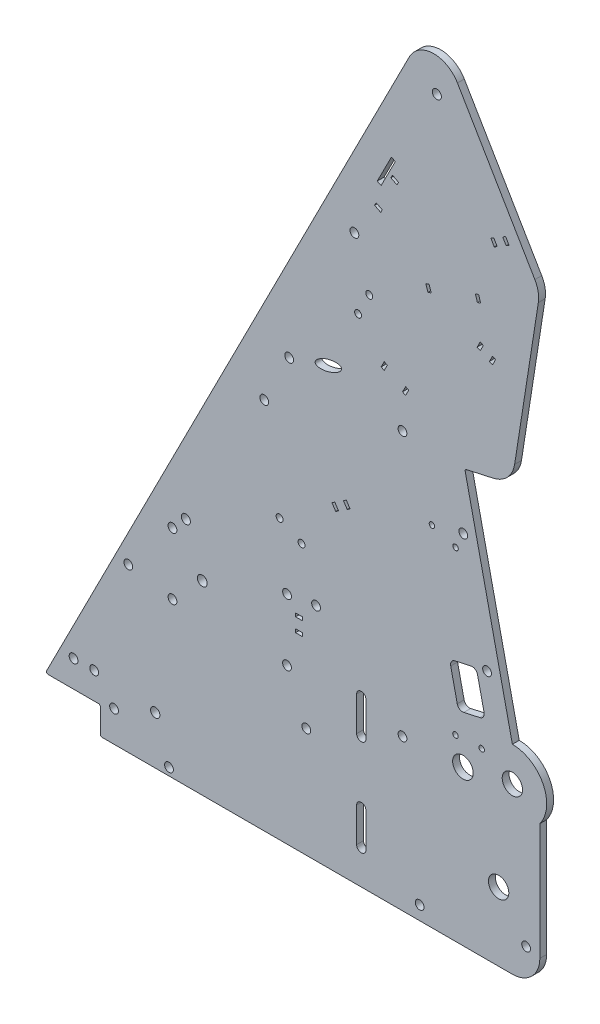
SolidWorks part; units mm, degrees
other "Markup1"
sketch "Sketch5"
ref_plane "Front Plane" through (0, 0, 0) normal (0, 0, 1) x (1, 0, 0)
ref_plane "Top Plane" through (0, 0, 0) normal (0, 1, 0) x (1, 0, 0)
ref_plane "Right Plane" through (0, 0, 0) normal (1, 0, 0) x (0, 0, -1)
sketch "Sketch1" plane through (0, 0, 0) normal (0, 0, 1) x (1, 0, 0)
  line L1 (228.6, -12.7) -> (228.6, 53.975)
  line L2 (178.7547, 351.4131) -> (0, 0)
  line L3 (228.6, 266.7) -> (178.7547, 351.4131)
  line L5 (0, 0) -> (25.4, 0)
  line L6 (25.4, 0) -> (25.4, -12.7)
  line L7 (25.4, -12.7) -> (228.6, -12.7)
  line L9 (215.9, 79.375) -> (193.9097, 178.5667)
  line L10 (193.9097, 178.5667) -> (215.6079, 183.377)
  line L11 (215.6079, 183.377) -> (228.6, 266.7)
  arc A0 (228.6, 53.975) -> (215.9, 79.375) centre (215.9, 63.5) ccw
  dimension "D7" = 12.7
  dimension "D8" = 76.2
  dimension "D10" = 31.75
  dimension "D2" = 279.4
  dimension "D3" = 25.4
  dimension "D4" = 215.9
  dimension "D5" = 394.2644
  dimension "D6" = 203.2
  dimension "D9" = 63.039
  dimension "D11" = 101.6
  dimension "D12" = 12.5
  dimension "D13" = 22.225
extrude "Boss-Extrude1" add sketch "Sketch1" along normal blind 3.175
sketch "Sketch2" plane through (0, 0, 3.175) normal (0, 0, 1) x (1, 0, 0)
  line L0 (178.7547, 351.4131) -> (0, 0) construction
  line L1 (25.4, -12.7) -> (228.6, -12.7) construction
  line L2 (215.9, 79.375) -> (193.9097, 178.5667) construction
  line L3 (193.9097, 178.5667) -> (215.6079, 183.377) construction
  line L4 (215.9, 79.375) -> (193.9097, 178.5667) construction
  line L5 (64.9432, 94.0578) -> (72.5445, 73.1732) construction
  line L6 (64.9432, 94.0578) -> (103.3734, 94.0578) construction
  line L10 (228.6, -12.7) -> (228.6, 53.975) construction
  circle A0 centre (64.9432, 94.0578) radius 2.0955
  circle A1 centre (180.975, 322.1643) radius 2.0955
  circle A2 centre (72.5445, 73.1732) radius 2.286
  circle A3 centre (193.2078, 152.3944) radius 2.032
  circle A4 centre (215.9, 63.5) radius 4.699
  circle A7 centre (173.0375, -6.35) radius 2.032
  circle A8 centre (204.203, 102.7985) radius 2.032
  circle A26 centre (209.55, 19.05) radius 4.699
  arc A30 (228.6, 53.975) -> (215.9, 79.375) centre (215.9, 63.5) ccw construction
  circle A31 centre (165.1, 179.3875) radius 2.032
  circle A35 centre (111.724, 87.4607) radius 2.032
  circle A36 centre (111.724, 58.8857) radius 2.032
  circle A37 centre (58.765, 58.8857) radius 2.032
  circle A38 centre (58.765, 87.4607) radius 2.032
  circle A39 centre (111.724, 58.8857) radius 1.905 construction
  circle A42 centre (111.724, 87.4607) radius 1.905 construction
  circle A43 centre (58.765, 58.8857) radius 1.905 construction
  circle A44 centre (58.765, 87.4607) radius 1.905 construction
  dimension "D3" = 4.191
  dimension "D5" = 4.191
  dimension "D9" = 4.572
  dimension "D20" = 9.398
  dimension "D23" = 9.398
  dimension "D18" = 4.064
  dimension "D26" = 4.064
  dimension "D14" = 4.064
  dimension "D10" = 4.064
  dimension "D2" = 15.24
  dimension "D6" = 15.24
  dimension "D7" = 22.225
  dimension "D21" = 44.45
  dimension "D22" = 6.35
  dimension "D19" = 160.3375
  dimension "D24" = 44.45
  dimension "D25" = 6.35
  dimension "D27" = 25.4
  dimension "D28" = 50.8
  dimension "D29" = 6.35
  dimension "D17" = 6.35
  dimension "D33" = 55.5625
  dimension "D15" = 114.3
  dimension "D4" = 180.975
  dimension "D8" = 70
extrude "Cut-Extrude1" cut sketch "Sketch2" against normal through all
sketch "Sketch7" plane through (0, 0, 3.175) normal (0, 0, 1) x (1, 0, 0)
  line L0 (146.05, 3.175) -> (146.05, 19.05) construction
  line L1 (143.891, 3.175) -> (143.891, 19.05)
  line L2 (148.209, 3.175) -> (148.209, 19.05)
  line L3 (146.05, 47.625) -> (146.05, 63.5) construction
  line L4 (143.891, 47.625) -> (143.891, 63.5)
  line L5 (148.209, 47.625) -> (148.209, 63.5)
  line L6 (25.4, -12.7) -> (228.6, -12.7) construction
  line L12 (228.6, -12.7) -> (228.6, 53.975) construction
  line L13 (25.4, -12.7) -> (228.6, -12.7) construction
  arc A0 (143.891, 3.175) -> (148.209, 3.175) centre (146.05, 3.175) ccw
  arc A1 (148.209, 19.05) -> (143.891, 19.05) centre (146.05, 19.05) ccw
  arc A2 (143.891, 47.625) -> (148.209, 47.625) centre (146.05, 47.625) ccw
  arc A3 (148.209, 63.5) -> (143.891, 63.5) centre (146.05, 63.5) ccw
  circle A8 centre (50.8, 9.525) radius 2.159
  point P2 (146.05, 11.1125)
  point P9 (146.05, 55.5625)
  dimension "D1" = 4.318
  dimension "D5" = 4.318
  dimension "D2" = 15.875
  dimension "D3" = 15.875
  dimension "D4" = 44.45
  dimension "D6" = 95.25
  dimension "D7" = 82.55
  dimension "D8" = 15.875
  dimension "D9" = 22.225
extrude "Cut-Extrude2" cut sketch "Sketch7" against normal through all
sketch "Sketch10" plane through (0, 0, 3.175) normal (0, 0, 1) x (1, 0, 0)
  circle A0 centre (120.65, 38.1) radius 2.032
  circle A1 centre (165.1, 57.15) radius 2.032
  circle A2 centre (13.0465, 12.3347) radius 2.032
  circle A3 centre (22.5715, 12.3347) radius 2.032
  circle A4 centre (38.3604, 62.564) radius 2.032
  circle A5 centre (13.0465, 12.3347) radius 2.032 construction
  circle A6 centre (22.5715, 12.3347) radius 2.032 construction
  dimension "D1" = 4.064
  dimension "D3" = 38.1
  dimension "D2" = 120.65
  dimension "D4" = 63.5
  dimension "D5" = 69.85
extrude "Cut-Extrude3" cut sketch "Sketch10" against normal up to next
fillet "Fillet1" radius 12.7 4 edges at (228.6, -12.7, 1.5875) (178.7547, 351.4131, 1.5875) (215.6079, 183.377, 1.5875) (228.6, 266.7, 1.5875)
fillet "Fillet2" radius 0.7937 4 edges at (25.4, -12.7, 1.5875) (25.4, 0, 1.5875) (193.9097, 178.5667, 1.5875) (0, 0, 1.5875)
sketch "Sketch12" plane through (0, 0, 3.175) normal (0, 0, 1) x (1, 0, 0)
  circle A0 centre (31.75, 1.5875) radius 2.032
  circle A1 centre (173.0375, -6.35) radius 2.032
  circle A2 centre (222.25, 1.5875) radius 2.032
  circle A3 centre (57.15, -9.2075) radius 2.032
  circle A4 centre (57.15, -9.2075) radius 2.286 construction
  dimension "D1" = 4.064
  dimension "D2" = 4.064
extrude "Cut-Extrude5" cut sketch "Sketch12" against normal through all
sketch "Sketch13" plane through (0, 0, 3.175) normal (0, 0, 1) x (1, 0, 0)
  line L1 (228.6, 0) -> (228.6, 53.975) construction
  line L3 (26.1937, -12.7) -> (215.9, -12.7) construction
  line L8 (177.4093, 244.3006) -> (175.8978, 243.8153)
  line L9 (178.3799, 241.2777) -> (177.4093, 244.3006)
  line L10 (176.8684, 240.7923) -> (178.3799, 241.2777)
  line L11 (175.8978, 243.8153) -> (176.8684, 240.7923)
  line L12 (177.4093, 244.3006) -> (175.8978, 243.8153)
  line L13 (178.3799, 241.2777) -> (177.4093, 244.3006)
  line L14 (176.8684, 240.7923) -> (178.3799, 241.2777)
  line L15 (175.8978, 243.8153) -> (176.8684, 240.7923)
  line L16 (159.9872, 286.5068) -> (153.4231, 273.6024)
  line L17 (199.7492, 248.1392) -> (201.2607, 248.6245)
  line L18 (198.7785, 251.1622) -> (199.7492, 248.1392)
  line L19 (200.29, 251.6475) -> (198.7785, 251.1622)
  line L20 (201.2607, 248.6245) -> (200.29, 251.6475)
  line L21 (199.7492, 248.1392) -> (201.2607, 248.6245)
  line L22 (198.7785, 251.1622) -> (199.7492, 248.1392)
  line L23 (200.29, 251.6475) -> (198.7785, 251.1622)
  line L24 (201.2607, 248.6245) -> (200.29, 251.6475)
  line L25 (159.9872, 286.5068) -> (161.7699, 285.6001)
  line L26 (159.73, 278.0885) -> (162.5599, 276.649)
  line L27 (160.4498, 279.5035) -> (159.73, 278.0885)
  line L28 (163.2797, 278.0639) -> (160.4498, 279.5035)
  line L29 (162.5599, 276.649) -> (163.2797, 278.0639)
  line L30 (159.73, 278.0885) -> (162.5599, 276.649)
  line L31 (160.4498, 279.5035) -> (159.73, 278.0885)
  line L32 (163.2797, 278.0639) -> (160.4498, 279.5035)
  line L33 (162.5599, 276.649) -> (163.2797, 278.0639)
  line L34 (153.4231, 273.6024) -> (155.2057, 272.6956)
  line L35 (161.7699, 285.6001) -> (155.2057, 272.6956)
  line L36 (152.9292, 264.7188) -> (152.2094, 263.3038)
  line L37 (155.7591, 263.2793) -> (152.9292, 264.7188)
  line L38 (155.0394, 261.8643) -> (155.7591, 263.2793)
  line L39 (152.2094, 263.3038) -> (155.0394, 261.8643)
  line L40 (152.9292, 264.7188) -> (152.2094, 263.3038)
  line L41 (155.7591, 263.2793) -> (152.9292, 264.7188)
  line L42 (155.0394, 261.8643) -> (155.7591, 263.2793)
  line L43 (152.2094, 263.3038) -> (155.0394, 261.8643)
  line L110 (153.132, 273.0302) -> (156.5324, 279.715) construction
  line L111 (154.9146, 272.1234) -> (158.315, 278.8082) construction
  line L122 (202.4699, 232.3383) -> (201.0549, 233.0581)
  line L123 (201.0304, 229.5084) -> (202.4699, 232.3383)
  line L124 (199.6154, 230.2282) -> (201.0304, 229.5084)
  line L125 (201.0549, 233.0581) -> (199.6154, 230.2282)
  line L126 (202.4699, 232.3383) -> (201.0549, 233.0581)
  line L127 (201.0304, 229.5084) -> (202.4699, 232.3383)
  line L128 (199.6154, 230.2282) -> (201.0304, 229.5084)
  line L129 (201.0549, 233.0581) -> (199.6154, 230.2282)
  line L130 (205.2752, 227.3491) -> (206.6902, 226.6294)
  line L131 (206.7147, 230.1791) -> (205.2752, 227.3491)
  line L132 (208.1297, 229.4593) -> (206.7147, 230.1791)
  line L133 (206.6902, 226.6294) -> (208.1297, 229.4593)
  line L134 (205.2752, 227.3491) -> (206.6902, 226.6294)
  line L135 (206.7147, 230.1791) -> (205.2752, 227.3491)
  line L136 (208.1297, 229.4593) -> (206.7147, 230.1791)
  line L137 (206.6902, 226.6294) -> (208.1297, 229.4593)
  line L138 (212.7746, 281.0741) -> (211.4063, 280.2691)
  line L139 (214.3847, 278.3377) -> (212.7746, 281.0741)
  line L140 (213.0165, 277.5326) -> (214.3847, 278.3377)
  line L141 (211.4063, 280.2691) -> (213.0165, 277.5326)
  line L142 (212.7746, 281.0741) -> (211.4063, 280.2691)
  line L143 (214.3847, 278.3377) -> (212.7746, 281.0741)
  line L144 (213.0165, 277.5326) -> (214.3847, 278.3377)
  line L145 (211.4063, 280.2691) -> (213.0165, 277.5326)
  line L146 (207.3017, 277.8539) -> (205.9335, 277.0488)
  line L147 (208.9118, 275.1174) -> (207.3017, 277.8539)
  line L148 (207.5436, 274.3124) -> (208.9118, 275.1174)
  line L149 (205.9335, 277.0488) -> (207.5436, 274.3124)
  line L150 (207.3017, 277.8539) -> (205.9335, 277.0488)
  line L151 (208.9118, 275.1174) -> (207.3017, 277.8539)
  line L152 (207.5436, 274.3124) -> (208.9118, 275.1174)
  line L153 (205.9335, 277.0488) -> (207.5436, 274.3124)
  line L184 (132.49, 134.4104) -> (134.221, 131.7488)
  line L185 (132.49, 134.4104) -> (133.8208, 135.2759)
  line L186 (134.221, 131.7488) -> (135.5518, 132.6143)
  line L187 (155.2281, 200.1197) -> (156.643, 199.3999)
  line L188 (156.6676, 202.9496) -> (155.2281, 200.1197)
  line L189 (158.0826, 202.2298) -> (156.6676, 202.9496)
  line L190 (156.643, 199.3999) -> (158.0826, 202.2298)
  line L191 (155.2281, 200.1197) -> (156.643, 199.3999)
  line L192 (156.6676, 202.9496) -> (155.2281, 200.1197)
  line L193 (158.0826, 202.2298) -> (156.6676, 202.9496)
  line L194 (156.643, 199.3999) -> (158.0826, 202.2298)
  line L195 (133.8208, 135.2759) -> (135.5518, 132.6143)
  line L196 (165.1328, 195.0814) -> (166.5478, 194.3617)
  line L197 (166.5723, 197.9113) -> (165.1328, 195.0814)
  line L198 (167.9873, 197.1916) -> (166.5723, 197.9113)
  line L199 (166.5478, 194.3617) -> (167.9873, 197.1916)
  line L200 (165.1328, 195.0814) -> (166.5478, 194.3617)
  line L201 (166.5723, 197.9113) -> (165.1328, 195.0814)
  line L202 (167.9873, 197.1916) -> (166.5723, 197.9113)
  line L203 (166.5478, 194.3617) -> (167.9873, 197.1916)
  line L204 (139.5442, 135.2109) -> (137.8132, 137.8725)
  line L205 (139.5442, 135.2109) -> (140.875, 136.0764)
  line L206 (137.8132, 137.8725) -> (139.144, 138.738)
  line L207 (140.875, 136.0764) -> (139.144, 138.738)
  line L209 (168.2448, 330.7518) -> (0.5868, 1.1536) construction
  line L210 (87.1862, 100.4607) -> (84.3562, 101.9002) construction
  line L288 (115.661, 81.8727) -> (118.836, 81.8727)
  line L289 (115.661, 81.8727) -> (115.661, 80.2852)
  line L290 (118.836, 81.8727) -> (118.836, 80.2852)
  line L291 (115.661, 80.2852) -> (118.836, 80.2852)
  line L292 (115.661, 75.5227) -> (118.836, 75.5227)
  line L293 (115.661, 75.5227) -> (115.661, 73.9352)
  line L294 (118.836, 75.5227) -> (118.836, 73.9352)
  line L295 (115.661, 73.9352) -> (118.836, 73.9352)
  line L297 (115.661, 86.2542) -> (115.661, 60.0922) construction
  line L298 (59.9715, 91.3977) -> (110.5175, 91.3977) construction
  circle A0 centre (112.7125, 182.5625) radius 2.032
  circle A2 centre (101.1964, 159.9231) radius 2.032 construction
  circle A3 centre (101.1964, 159.9231) radius 2.032
  circle A4 centre (144.5649, 216.046) radius 1.6 construction
  circle A5 centre (149.7335, 226.2069) radius 1.6 construction
  circle A7 centre (144.5649, 216.046) radius 1.6
  circle A8 centre (149.7335, 226.2069) radius 1.6
  circle A9 centre (108.294, 116.1502) radius 1.6 construction
  circle A10 centre (118.455, 110.9816) radius 1.6 construction
  circle A11 centre (108.294, 116.1502) radius 1.6
  circle A12 centre (118.455, 110.9816) radius 1.6
  circle A13 centre (142.875, 247.65) radius 2.032 construction
  circle A14 centre (142.875, 247.65) radius 2.032
  ellipse E0 centre (130.8261, 188.4615) end of major axis (136.864, 190.4279) minor radius 2.3812 construction
  ellipse E1 centre (130.8261, 188.4615) end of major axis (136.864, 190.4279) minor radius 2.3812
  point P44 (0, 0)
  dimension "D2" = 4.064
  dimension "D1" = 195.2625
  dimension "D6" = 115.8875
  dimension "D11" = 7.62
  dimension "D12" = 6.858
  dimension "D13" = 1.5875
  dimension "D14" = 3.175
  dimension "D15" = 4.7625
  dimension "D16" = 60
  dimension "D17" = 57.15
  dimension "D24" = 50.8
  dimension "D29" = 3.175
  dimension "D30" = 1.5875
  dimension "D31" = 4.7625
  dimension "D32" = 0
  dimension "D33" = 9.525
  dimension "D7" = 0
  dimension "D8" = 0
  dimension "D9" = 0
  dimension "D10" = 0
  dimension "D18" = 0
  dimension "D19" = 0
  dimension "D20" = 0
  dimension "D21" = 0
  dimension "D22" = 0
  dimension "D23" = 0
extrude "Cut-Extrude6" cut sketch "Sketch13" against normal through all
sketch "Sketch14" plane through (0, 0, 3.175) normal (0, 0, 1) x (1, 0, 0)
  line L5 (186.8444, 98.9502) -> (199.2434, 101.699)
  line L6 (186.8444, 98.9502) -> (190.9676, 80.3518)
  line L7 (190.9676, 80.3518) -> (203.3665, 83.1006)
  line L8 (199.2434, 101.699) -> (203.3665, 83.1006)
  line L14 (202.8168, 85.5804) -> (199.7931, 99.2192) construction
  line L15 (193.4474, 80.9015) -> (200.8868, 82.5508) construction
  line L16 (187.3942, 96.4704) -> (190.4178, 82.8316) construction
  line L17 (196.7636, 101.1493) -> (189.3242, 99.5) construction
  circle A0 centre (189.6022, 69.9806) radius 1.27
  circle A1 centre (201.7089, 70.5092) radius 1.27
  circle A2 centre (189.6022, 69.9806) radius 1.27 construction
  circle A3 centre (201.7089, 70.5092) radius 1.27 construction
  circle A4 centre (165.1, 57.15) radius 2.032
  circle A5 centre (125.1498, 89.5229) radius 2.032
  circle A6 centre (178.7216, 148.5324) radius 1.27
  circle A8 centre (178.7216, 148.5324) radius 1.27 construction
  circle A9 centre (189.6226, 145.0954) radius 1.27
  circle A10 centre (189.6226, 145.0954) radius 1.27 construction
  point P8 (152.4, 88.9)
  dimension "D1" = 4.064
extrude "Cut-Extrude7" cut sketch "Sketch14" against normal through all both and the other way through all
fillet "Fillet3" radius 2.54 4 edges at (199.2434, 101.699, 1.5875) (186.8444, 98.9502, 1.5875) (190.9676, 80.3518, 1.5875) (203.3665, 83.1006, 1.5875)
sketch "Sketch15" plane through (0, 0, 3.175) normal (0, 0, 1) x (1, 0, 0)
  circle A0 centre (193.04, 58.801) radius 4.7625 construction
  circle A1 centre (193.04, 58.801) radius 4.7625
extrude "Cut-Extrude8" cut sketch "Sketch15" against normal through all
equation "\"D6@Sketch2\"=\"D2@Sketch2\""
